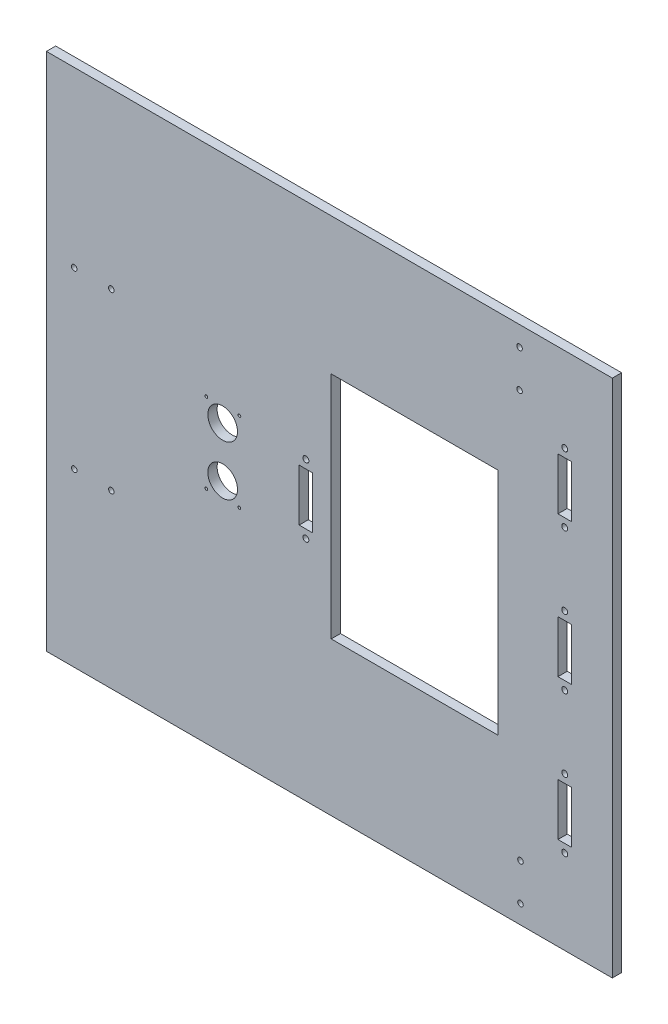
SolidWorks part; units mm, degrees
ref_plane "Plan de face" through (0, 0, 0) normal (0, 0, 1) x (1, 0, 0)
ref_plane "Plan de dessus" through (0, 0, 0) normal (0, 1, 0) x (1, 0, 0)
ref_plane "Plan de droite" through (0, 0, 0) normal (1, 0, 0) x (0, 0, -1)
sketch "Esquisse1" plane through (0, 0, 0) normal (0, 0, 1) x (1, 0, 0)
  line L1 (0, 0) -> (305, 0)
  line L2 (0, 0) -> (0, 280)
  line L3 (0, 280) -> (305, 280)
  line L4 (305, 0) -> (305, 280)
  dimension "D1" = 280
  dimension "D2" = 305
extrude "Boss.-Extru.1" add sketch "Esquisse1" along normal blind 5
sketch "Esquisse2" plane through (0, 0, 5) normal (0, 0, 1) x (1, 0, 0)
  line L0 (305, 0) -> (305, 280) construction
  line L1 (153.5, 206.22) -> (243.5, 206.22)
  line L2 (153.5, 206.22) -> (153.5, 82.52)
  line L3 (153.5, 82.52) -> (243.5, 82.52)
  line L4 (243.5, 206.22) -> (243.5, 82.52)
  line L5 (305, 280) -> (0, 280) construction
  line L6 (0, 0) -> (305, 0) construction
  point P10 (153.5, 144.37)
  dimension "D1" = 61.5
  dimension "D2" = 73.78
  dimension "D3" = 82.52
  dimension "D4" = 90
extrude "Enlèv. mat.-Extru.1" cut sketch "Esquisse2" against normal blind 5
sketch "Esquisse3" plane through (0, 0, 0) normal (0, 0, -1) x (-1, 0, 0)
  circle A0 centre (-15, 92.5) radius 1.5
  circle A1 centre (-35, 92.5) radius 1.5
  circle A2 centre (-35, 186.5) radius 1.5
  circle A3 centre (-15, 186.5) radius 1.5
  circle A4 centre (-255, 249.4) radius 1.5
  circle A5 centre (-255, 269.4) radius 1.5
  circle A6 centre (-255.5, 10) radius 1.5
  circle A7 centre (-255.5, 30) radius 1.5
  dimension "D1" = 3
extrude "Enlèv. mat.-Extru.2" cut sketch "Esquisse3" against normal through all
sketch "Esquisse4" plane through (0, 0, 5) normal (0, 0, 1) x (1, 0, 0)
  line L0 (305, 0) -> (305, 280) construction
  line L1 (275.7, 50) -> (283, 50)
  line L2 (275.7, 50) -> (275.7, 78)
  line L3 (275.7, 78) -> (283, 78)
  line L4 (283, 50) -> (283, 78)
  line L5 (275.7, 126) -> (283, 126)
  line L6 (275.7, 126) -> (275.7, 154)
  line L7 (275.7, 154) -> (283, 154)
  line L8 (283, 126) -> (283, 154)
  line L9 (275.7, 202) -> (283, 202)
  line L10 (275.7, 202) -> (275.7, 230)
  line L11 (275.7, 230) -> (283, 230)
  line L12 (283, 202) -> (283, 230)
  line L13 (0, 0) -> (305, 0) construction
  line L14 (305, 280) -> (0, 280) construction
  line L15 (153.5, 206.22) -> (153.5, 82.52) construction
  line L16 (136.2, 127) -> (143.5, 127)
  line L17 (136.2, 127) -> (136.2, 155)
  line L18 (136.2, 155) -> (143.5, 155)
  line L19 (143.5, 127) -> (143.5, 155)
  line L20 (139.85, 117.3791) -> (139.85, 165.7171) construction
  line L21 (279.35, 33.1371) -> (279.35, 261.3707) construction
  circle A0 centre (139.85, 159.5) radius 1.6
  circle A1 centre (139.85, 122.5) radius 1.6
  circle A2 centre (279.35, 82.5) radius 1.6
  circle A3 centre (279.35, 45.5) radius 1.6
  circle A4 centre (279.35, 121.5) radius 1.6
  circle A5 centre (279.35, 158.5) radius 1.6
  circle A6 centre (279.35, 197.5) radius 1.6
  circle A7 centre (279.35, 234.5) radius 1.6
  point P12 (279.35, 50)
  point P13 (279.35, 126)
  point P14 (279.35, 154)
  point P15 (279.35, 230)
  point P18 (275.7, 140)
  dimension "D20" = 3.2
  dimension "D21" = 3.2
  dimension "D23" = 3.2
  dimension "D24" = 3.2
  dimension "D25" = 3.2
  dimension "D26" = 3.2
  dimension "D27" = 3.2
  dimension "D28" = 3.2
  dimension "D29" = 4.5
  dimension "D30" = 4.5
  dimension "D31" = 4.5
  dimension "D32" = 4.5
  dimension "D33" = 4.5
  dimension "D34" = 4.5
  dimension "D1" = 28
  dimension "D2" = 28
  dimension "D3" = 28
  dimension "D4" = 7.3
  dimension "D5" = 7.3
  dimension "D6" = 7.3
  dimension "D7" = 22
  dimension "D8" = 22
  dimension "D9" = 22
  dimension "D10" = 140
  dimension "D11" = 50
  dimension "D12" = 50
  dimension "D13" = 28
  dimension "D14" = 7.3
  dimension "D15" = 125
  dimension "D16" = 10
  dimension "D17" = 3.65
  dimension "D18" = 4.5
  dimension "D19" = 4.5
  dimension "D22" = 3.65
extrude "Enlèv. mat.-Extru.3" cut sketch "Esquisse4" against normal through all
sketch "Esquisse5" plane through (0, 0, 5) normal (0, 0, 1) x (1, 0, 0)
  line L0 (305, 0) -> (305, 280) construction
  line L1 (0, 0) -> (305, 0) construction
  line L2 (85, 163) -> (85, 118) construction
  line L4 (85, 163) -> (105, 163) construction
  line L5 (105, 163) -> (105, 118) construction
  line L6 (105, 118) -> (85, 118) construction
  circle A0 centre (95, 127) radius 8
  circle A1 centre (95, 154) radius 8
  circle A2 centre (86.2, 162) radius 0.75
  circle A3 centre (104, 162) radius 0.75
  circle A4 centre (104, 119) radius 0.75
  circle A5 centre (86.2, 119) radius 0.75
  dimension "D1" = 27
  dimension "D2" = 16
  dimension "D3" = 16
  dimension "D4" = 210
  dimension "D5" = 210
  dimension "D6" = 127
  dimension "D7" = 20
  dimension "D8" = 45
  dimension "D9" = 1.5
  dimension "D10" = 1.5
  dimension "D11" = 1.5
  dimension "D12" = 1.5
  dimension "D13" = 9
  dimension "D14" = 10
  dimension "D15" = 1
  dimension "D16" = 1
  dimension "D17" = 1
  dimension "D18" = 1.2
  dimension "D19" = 1
  dimension "D20" = 1.2
  dimension "D21" = 1
  dimension "D22" = 1
extrude "Enlèv. mat.-Extru.4" cut sketch "Esquisse5" against normal through all
